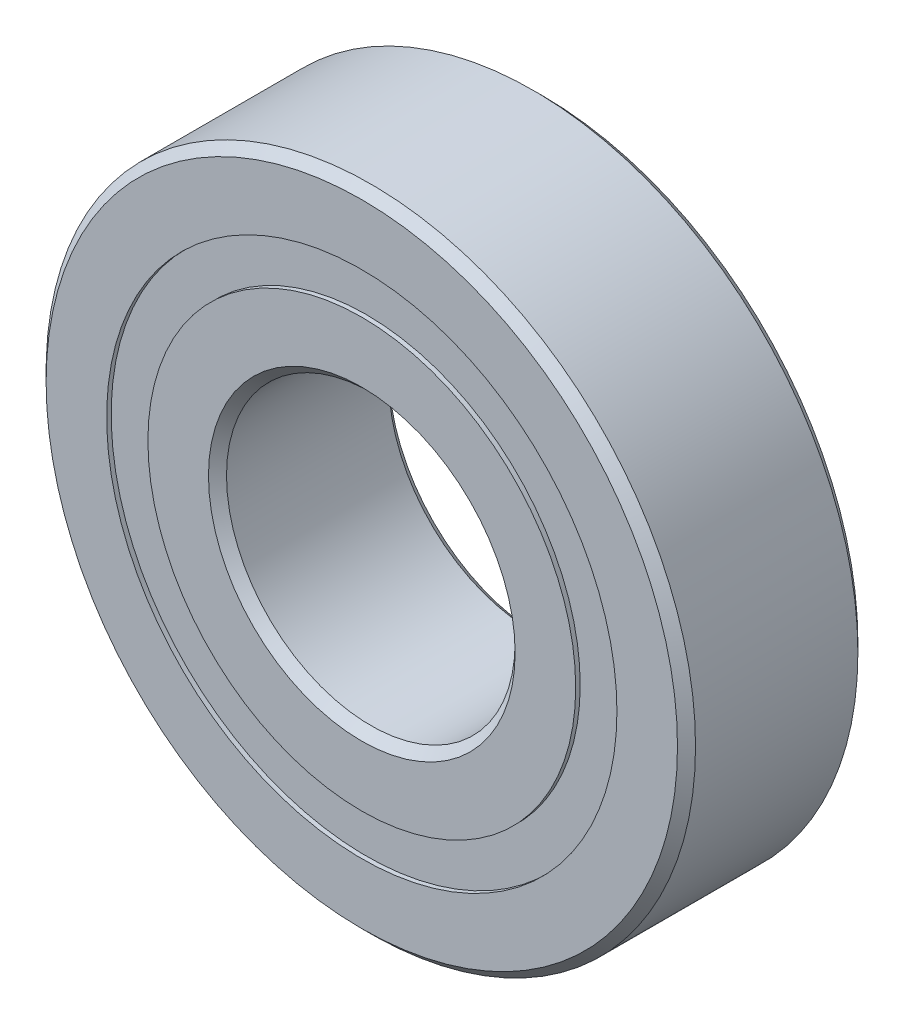
SolidWorks part; units mm, degrees
ref_plane "Front Plane" through (0, 0, 0) normal (0, 0, 1) x (1, 0, 0)
ref_plane "Top Plane" through (0, 0, 0) normal (0, 1, 0) x (1, 0, 0)
ref_plane "Right Plane" through (0, 0, 0) normal (1, 0, 0) x (0, 0, -1)
sketch "Sketch1" plane through (0, 0, 0) normal (1, 0, 0) x (0, 0, -1)
  line L0 (-3.9688, 0) -> (3.9688, 0) construction
  line L1 (0, 14.2875) -> (0, -14.2875) construction
  line L2 (3.5719, 14.2875) -> (-3.5719, 14.2875)
  line L3 (-3.5719, 14.2875) -> (-3.9688, 13.8906)
  line L4 (-3.9688, 13.8906) -> (-3.9688, 11.2259)
  line L5 (-3.9688, 11.2259) -> (-1.7639, 11.2259)
  line L6 (3.9687, 11.2259) -> (1.7639, 11.2259)
  line L7 (3.9687, 13.8906) -> (3.9687, 11.2259)
  line L8 (3.5719, 14.2875) -> (3.9687, 13.8906)
  line L9 (0, 14.2875) -> (0, 10.3187) construction
  line L10 (0, 10.3187) -> (0, 6.35) construction
  arc A0 (-1.7639, 11.2259) -> (1.7639, 11.2259) centre (0, 10.3187) cw
  point P14 (0, 6.35)
  dimension "D3" = 3.5278
  dimension "D1" = 45
  dimension "Width" = 7.9375
  dimension "OD" = 28.575
  dimension "D2" = 0.3969
  dimension "Shaft Dia" = 12.7
  dimension "D4" = 0.9071
revolve "Revolve1" add sketch "Sketch1" angle 360 about L0
sketch "Sketch3" plane through (0, 0, 0) normal (1, 0, 0) x (0, 0, -1)
  line L0 (-3.9688, 9.4116) -> (-1.7639, 9.4116)
  line L1 (0, 14.2875) -> (0, -14.2875) construction
  line L2 (-3.9688, 13.8906) -> (-3.9688, 11.2259) construction
  line L3 (-3.9688, 9.4116) -> (-3.9688, 6.7469)
  line L4 (-3.5719, 14.2875) -> (-3.9688, 13.8906) construction
  line L5 (-3.9688, 6.7469) -> (-3.5719, 6.35)
  line L6 (-3.5719, 6.35) -> (3.5719, 6.35)
  line L7 (3.5719, 14.2875) -> (3.5719, -14.2875) construction
  line L8 (3.5719, 6.35) -> (3.9688, 6.7469)
  line L9 (3.9688, -13.8906) -> (3.9688, 13.8906) construction
  line L10 (3.9688, 6.7469) -> (3.9688, 9.4116)
  line L11 (3.9688, 9.4116) -> (1.7639, 9.4116)
  line L13 (3.5719, 14.2875) -> (3.9687, 13.8906) construction
  arc A0 (1.7639, 11.2259) -> (-1.7639, 11.2259) centre (0, 10.3187) ccw construction
  arc A1 (1.7639, 9.4116) -> (-1.7639, 9.4116) centre (0, 10.3187) cw
revolve "Revolve3" add sketch "Sketch3" angle 360 about L0
sketch "Sketch4" plane through (0, 0, 0) normal (1, 0, 0) x (0, 0, -1)
  line L0 (-1.9835, 10.3187) -> (1.9835, 10.3187)
  arc A2 (-1.9835, 10.3187) -> (1.9835, 10.3187) centre (0, 10.3187) cw
  arc A3 (1.7639, 11.2259) -> (-1.7639, 11.2259) centre (0, 10.3187) ccw construction
revolve "Revolve4" add sketch "Sketch4" angle 360 about L0
ref_axis "Axis1" through (0, 0, -3.9688) along (0, 0, 1)
pattern_circular "CirPattern1" count 10 every 36 about axis through (0, 0, -3.9688) along (0, 0, 1) of bodies 104
sketch "Sketch5" plane through (0, 0, 0) normal (1, 0, 0) x (0, 0, -1)
  line L0 (-3.9688, 11.2259) -> (-1.7639, 11.2259) construction
  line L1 (-3.7703, 11.2259) -> (-1.9835, 11.2259)
  line L2 (-3.7703, 11.2259) -> (-3.7703, 9.4116)
  line L3 (-3.7703, 9.4116) -> (-1.9835, 9.4116)
  line L4 (-1.9835, 11.2259) -> (-1.9835, 9.4116)
  line L5 (-3.9688, 9.4116) -> (-1.7639, 9.4116) construction
  line L6 (3.9687, 11.2259) -> (1.7639, 11.2259) construction
  line L7 (3.7703, 11.2259) -> (1.9835, 11.2259)
  line L8 (3.7703, 11.2259) -> (3.7703, 9.4116)
  line L9 (3.7703, 9.4116) -> (1.9835, 9.4116)
  line L10 (1.9835, 11.2259) -> (1.9835, 9.4116)
  line L11 (3.9688, 9.4116) -> (1.7639, 9.4116) construction
  line L12 (-3.5719, 14.2875) -> (-3.9688, 13.8906) construction
  point P18 (-3.7703, 14.0891)
revolve "Revolve5" add sketch "Sketch5" angle 360 about L0
equation "\"D2@Sketch1\" = \"Width@Sketch1\"*.05"
equation "\"D3@Sketch1\" = \"Width@Sketch1\"/2.25"
equation "\"D4@Sketch1\" = (((\"OD@Sketch1\"-\"Width@Sketch1\")/2)/3.25)/3.5"
equation "\"D2@CirPattern1\" = 360/\"Balls@CirPattern1\""
